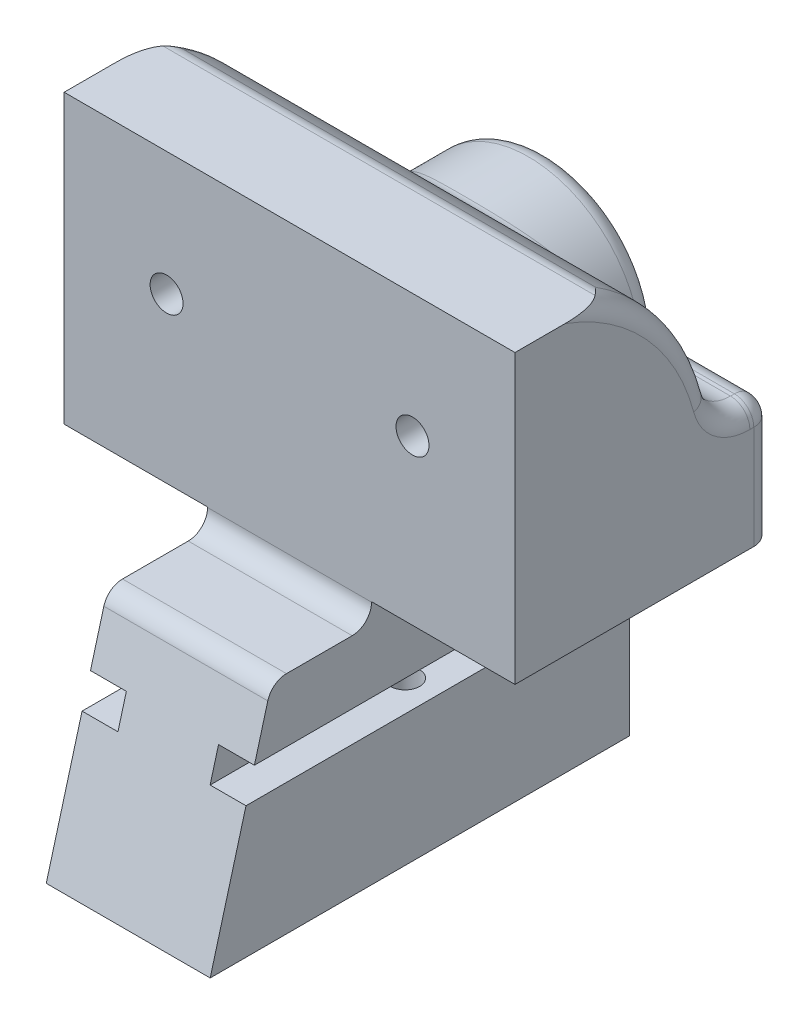
SolidWorks part; units mm, degrees
ref_plane "Alzado" through (0, 0, 0) normal (0, 0, 1) x (1, 0, 0)
ref_plane "Planta" through (0, 0, 0) normal (0, 1, 0) x (1, 0, 0)
ref_plane "Vista lateral" through (0, 0, 0) normal (1, 0, 0) x (0, 0, -1)
sketch "Croquis1" plane through (0, 0, 0) normal (0, 0, 1) x (1, 0, 0)
  line L0 (0, -22.27) -> (0, -45.2962) construction
  line L9 (-34.925, 22.27) -> (34.925, 22.27)
  line L10 (-34.925, 22.27) -> (-34.925, -22.27)
  line L11 (-34.925, -22.27) -> (34.925, -22.27)
  line L12 (34.925, 22.27) -> (34.925, -22.27)
  line L13 (-34.925, 22.27) -> (34.925, -22.27) construction
  line L14 (-34.925, -22.27) -> (34.925, 22.27) construction
  line L15 (-12.7, -60.27) -> (12.7, -60.27)
  line L16 (-12.7, -60.27) -> (-12.7, -22.27)
  line L17 (-12.7, -22.27) -> (12.7, -22.27)
  line L18 (12.7, -60.27) -> (12.7, -22.27)
  line L19 (-12.7, -60.27) -> (12.7, -22.27) construction
  line L20 (-12.7, -22.27) -> (12.7, -60.27) construction
  line L21 (-12.7, -35.15) -> (-7.14, -35.15)
  line L22 (-12.7, -35.15) -> (-12.7, -39.93)
  line L23 (-12.7, -39.93) -> (-7.14, -39.93)
  line L24 (-7.14, -35.15) -> (-7.14, -39.93)
  line L25 (12.7, -39.93) -> (7.14, -39.93)
  line L26 (7.14, -35.15) -> (7.14, -39.93)
  line L27 (12.7, -35.15) -> (7.14, -35.15)
  point P0 (0, 0)
  point P5 (0, -41.27)
  dimension "D1" = 69.85
  dimension "D2" = 44.54
  dimension "D3" = 25.4
  dimension "D4" = 38
  dimension "D5" = 12.88
  dimension "D6" = 4.78
  dimension "D7" = 5.56
extrude "Saliente-Extruir1" add sketch "Croquis1" against normal blind 40 contours L12 L9 L10 L11 | L27 L18 L11 L16 L21 L24 L23 L15 L25 L26 region at (0, 0, 0) region at (0, -41.4874, 0)
sketch "Croquis2" plane through (34.925, 0, 0) normal (1, 0, 0) x (0, 0, -1)
  line L0 (14.7115, 22.27) -> (40, 22.27)
  line L1 (40, 22.27) -> (0, 22.27) construction
  line L2 (40, 22.27) -> (40, -3.27)
  line L3 (40, 22.27) -> (40, -22.27) construction
  line L4 (40, -3.27) -> (31.4641, -3.27)
  line L5 (40, -22.27) -> (0, -22.27) construction
  line L6 (0, 22.27) -> (0, -22.27) construction
  arc A0 (14.7115, 22.27) -> (31.4641, -3.27) centre (-3.18, -7.73) cw
  point P12 (0, 0)
  dimension "D1" = 19
  dimension "D2" = 34.93
  dimension "D3" = 30
  dimension "D4" = 3.18
extrude "Cortar-Extruir1" cut sketch "Croquis2" against normal through all
sketch "Croquis3" plane through (0, 0, -40) normal (0, 0, -1) x (-1, 0, 0)
  line L0 (-17.46, -4.87) -> (17.46, -4.87)
  line L1 (17.46, -4.87) -> (0, 0) construction
  line L2 (0, 0) -> (0, -60.27) construction
  line L3 (12.7, -60.27) -> (-12.7, -60.27) construction
  line L4 (34.925, -3.27) -> (-34.925, -3.27) construction
  arc A0 (-17.46, -4.87) -> (17.46, -4.87) centre (0, -4.87) cw
  point P3 (0, 0)
  point P11 (0, 0)
  dimension "D1" = 17.46
  dimension "D2" = 1.6
fillet "Redondeo1" radius 6 1 edges at (0, -3.27, -31.4641)
extrude "Saliente-Extruir2" add sketch "Croquis3" against normal up to next contours A0 L0
fillet "Redondeo2" radius 3 5 edges at (17.3865, -3.27, -38.1954) (17.2186, -1.9769, -32.6699) (-2.7183, 12.3771, -25.3824) (-17.2219, -1.9965, -32.6949) (-17.3865, -3.27, -38.1954)
fillet "Redondeo3" radius 3 5 edges at (27.4306, -3.27, -40) (18.0685, -2.6177, -40) (0, 12.59, -40) (-18.0685, -2.6177, -40) (-27.4306, -3.27, -40)
fillet "Redondeo5" radius 3 11 edges at (34.925, -14.27, -40) (34.925, -4.1487, -39.1213) (34.925, -2.024, -32.7303) (-34.925, -14.27, -40) (-34.925, -4.1487, -39.1213) (-34.925, -2.024, -32.7303) (34.925, 13.2903, -24.7172) (0, 22.27, -14.7115) (-34.925, 13.2903, -24.7172) (34.925, -3.27, -36.6954) (-34.925, -3.27, -36.6954)
sketch "Croquis7" plane through (12.7, 0, 0) normal (1, 0, 0) x (0, 0, -1)
  line L0 (0, -25.34) -> (-15.4704, -25.34)
  line L1 (0, -35.15) -> (0, -22.27) construction
  line L2 (-15.4704, -25.34) -> (-25, -60.27)
  line L3 (-25, -60.27) -> (0, -60.27)
  line L4 (0, -25.34) -> (0, -60.27)
  dimension "D1" = 74.74
  dimension "D2" = 34.93
  dimension "D3" = 65
extrude "Saliente-Extruir3" add sketch "Croquis7" against normal up to surface (25.4 mm away) up to face at (-12.7, -50.1, -20)
sketch "Croquis8" plane through (0, 0, -40) normal (0, 0, -1) x (-1, 0, 0)
  line L0 (12.7, -39.93) -> (12.7, -35.15) construction
  line L1 (12.7, -35.15) -> (7.14, -35.15) construction
  line L2 (7.14, -35.15) -> (7.14, -39.93) construction
  line L3 (7.14, -39.93) -> (12.7, -39.93) construction
  line L4 (-12.7, -35.15) -> (-12.7, -39.93) construction
  line L5 (-12.7, -39.93) -> (-7.14, -39.93) construction
  line L6 (-7.14, -39.93) -> (-7.14, -35.15) construction
  line L7 (-7.14, -35.15) -> (-12.7, -35.15) construction
  line L8 (12.7, -39.93) -> (12.7, -35.15)
  line L9 (12.7, -35.15) -> (7.14, -35.15)
  line L10 (7.14, -35.15) -> (7.14, -39.93)
  line L11 (7.14, -39.93) -> (12.7, -39.93)
  line L12 (-12.7, -35.15) -> (-12.7, -39.93)
  line L13 (-12.7, -39.93) -> (-7.14, -39.93)
  line L14 (-7.14, -39.93) -> (-7.14, -35.15)
  line L15 (-7.14, -35.15) -> (-12.7, -35.15)
extrude "Cortar-Extruir2" cut sketch "Croquis8" against normal through all
fillet "Redondeo6" radius 3 2 edges at (0, -25.34, 15.4704) (0, -25.34, 0)
hole_wizard "Taladros de espiga de 3/4 (0.7500)1" positions "Croquis17" profile "Croquis19" hole size "3/4" standard "Ansi Inch"
sketch "Croquis17" plane through (0, 0, -40) normal (0, 0, -1) x (-1, 0, 0)
  arc A0 (14.0898, -1.619) -> (-14.0898, -1.619) centre (0, -4.87) ccw construction
  point P0 (0, -4.87)
  point P3 (0, 0)
sketch "Croquis19" plane through (0, -4.87, -40) normal (1, 0, 0) x (0, 1, 0)
  line L0 (0, 0) -> (0, 35.7232)
  line L1 (0, 35.7232) -> (9.525, 30)
  line L2 (9.525, 30) -> (9.525, 0)
  line L5 (9.525, 0) -> (0, 0)
  line L10 (0, 35.7232) -> (-9.525, 30) construction
  line L11 (0, -6.35) -> (0, 107.95) construction
  dimension "Diámetro de taladro" = 19.05
  dimension "Profundidad de taladro" = 30
  dimension "Ángulo de perforador" = 118
hole_wizard "Taladro roscado 1/4-201" positions "Croquis20" profile "Croquis21" tap size "1/4-20" standard "Ansi Inch"
sketch "Croquis20" plane through (0, 0, 0) normal (0, 0, 1) x (1, 0, 0)
  line L0 (12.7, -22.27) -> (34.925, -22.27) construction
  line L1 (34.925, 22.27) -> (34.925, -22.27) construction
  point P0 (19.045, 3.13)
  point P2 (-19.055, 3.13)
  point P7 (0, 0)
  point P10 (0, 0)
  dimension "D1" = 38.1
  dimension "D2" = 25.4
  dimension "D3" = 15.88
sketch "Croquis21" plane through (19.045, 3.13, 0) normal (1, 0, 0) x (0, -1, 0)
  line L0 (0, 0) -> (0, 23.8838)
  line L1 (0, 23.8838) -> (2.5527, 22.35)
  line L2 (2.5527, 22.35) -> (2.5527, 0)
  line L5 (2.5527, 0) -> (0, 0)
  line L10 (0, 23.8838) -> (-2.5527, 22.35) construction
  line L11 (0, -6.35) -> (0, 107.95) construction
  dimension "Diámetro de perforador para roscar" = 5.1054
  dimension "Profundidad de perforador para roscar" = 22.35
  dimension "Ángulo de perforador" = 118
cosmetic thread "Rosca de taladro1" parameters "D1"=16, "D2"=6.35
cosmetic thread "Rosca de taladro2" parameters "D1"=16, "D2"=6.35
hole_wizard "Diámetro de taladro #25 (0.1495)1" positions "Croquis24" profile "Croquis25" hole size "#25" standard "Progressive"
sketch "Croquis24" plane through (0, -60.27, 0) normal (0, -1, 0) x (-1, 0, 0)
  line L0 (0, 0) -> (0, 40) construction
  line L1 (12.7, 40) -> (-12.7, 40) construction
  point P0 (-7.9, 10)
  point P2 (7.9, 10)
  point P12 (0, 0)
  dimension "D1" = 15.8
  dimension "D2" = 30
sketch "Croquis25" plane through (7.9, -60.27, -10) normal (1, 0, 0) x (0, 0, -1)
  line L0 (0, 0) -> (0, 28.1408)
  line L1 (0, 28.1408) -> (1.8986, 27)
  line L2 (1.8986, 27) -> (1.8986, 0)
  line L5 (1.8986, 0) -> (0, 0)
  line L10 (0, 28.1408) -> (-1.8987, 27) construction
  line L11 (0, -6.35) -> (0, 107.95) construction
  dimension "Diámetro de taladro" = 3.7973
  dimension "Profundidad de taladro" = 27
  dimension "Ángulo de perforador" = 118
hole_wizard "Taladro roscado #12-241" positions "Croquis26" profile "Croquis27" tap size "#12-24" standard "Progressive"
sketch "Croquis26" plane through (0, -60.27, 0) normal (0, -1, 0) x (-1, 0, 0)
  point P0 (7.9, 10)
  point P3 (-7.9, 10)
sketch "Croquis27" plane through (-7.9, -60.27, -10) normal (1, 0, 0) x (0, 0, -1)
  line L0 (0, 0) -> (0, 25.8507)
  line L1 (0, 25.8507) -> (2.2479, 24.5)
  line L2 (2.2479, 24.5) -> (2.2479, 0)
  line L5 (2.2479, 0) -> (0, 0)
  line L10 (0, 25.8507) -> (-2.2479, 24.5) construction
  line L11 (0, -6.35) -> (0, 107.95) construction
  dimension "Diámetro de perforador para roscar" = 4.4958
  dimension "Profundidad de perforador para roscar" = 24.5
  dimension "Ángulo de perforador" = 118
cosmetic thread "Rosca de taladro3" parameters "D1"=19, "D2"=5.4864
cosmetic thread "Rosca de taladro4" parameters "D1"=19, "D2"=5.4864
